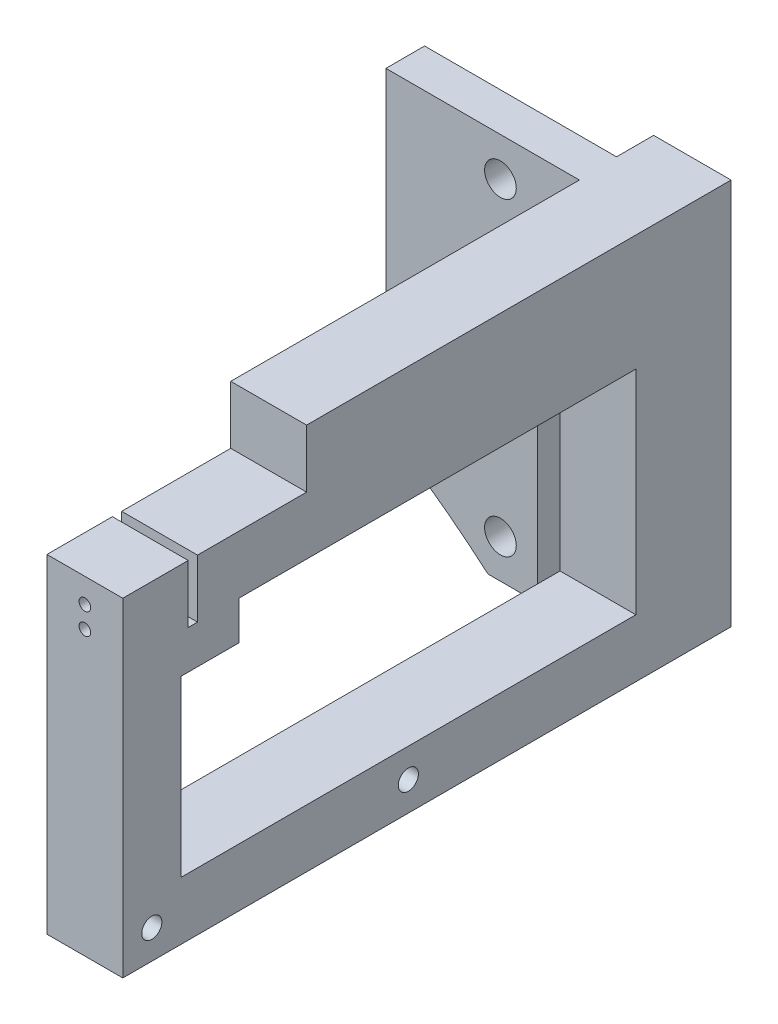
SolidWorks part; units mm, degrees
ref_plane "Front Plane" through (0, 0, 0) normal (0, 0, 1) x (1, 0, 0)
ref_plane "Top Plane" through (0, 0, 0) normal (0, 1, 0) x (1, 0, 0)
ref_plane "Right Plane" through (0, 0, 0) normal (1, 0, 0) x (0, 0, -1)
sketch "Sketch1" plane through (0, 0, 0) normal (0, 0, 1) x (1, 0, 0)
  line L0 (95.25, -31.75) -> (86.8503, -31.75) construction
  line L1 (94.996, -31.75) -> (86.8503, -31.75)
  line L2 (70.104, -19.2524) -> (70.104, -19.41)
  line L32 (70.104, 22.225) -> (70.104, 31.75)
  line L33 (70.104, -19.2524) -> (70.104, 22.225)
  line L34 (70.104, -19.2524) -> (70.104, 22.225)
  line L35 (101.6, 31.75) -> (3.175, 31.75) construction
  line L36 (101.6, 22.479) -> (101.6, 31.75)
  line L54 (70.104, 31.75) -> (101.6, 31.75)
  line L58 (94.996, 22.479) -> (101.6, 22.479)
  line L59 (94.996, -31.75) -> (94.996, 22.479)
  line L60 (94.996, 22.479) -> (101.6, 22.479)
  line L61 (94.996, -31.75) -> (94.996, 22.479)
  circle A0 centre (88.9, -25.4) radius 2.6 construction
  circle A1 centre (88.9, -25.4) radius 2.6
  circle A6 centre (88.9, 25.4) radius 2.6 construction
  circle A7 centre (88.9, 25.4) radius 2.6
  arc A8 (86.8503, -31.75) -> (69.85, -19.2524) centre (0, -132.08) ccw construction
  arc A9 (86.8503, -31.75) -> (70.104, -19.41) centre (0, -132.08) ccw
  dimension "D2" = 0.254
  dimension "D3" = 0.254
extrude "Boss-Extrude1" add sketch "Sketch1" along normal blind 6.35
sketch "Sketch2" plane through (0, 0, 6.35) normal (0, 0, 1) x (1, 0, 0)
  line L0 (101.6, 22.479) -> (101.854, 22.479)
  line L1 (94.996, 22.479) -> (101.6, 22.479) construction
  line L2 (101.854, 22.479) -> (101.854, -31.75)
  line L3 (101.854, -31.75) -> (114.3, -31.75)
  line L4 (114.3, -31.75) -> (114.3, 31.75)
  line L5 (114.3, 31.75) -> (101.6, 31.75)
  line L6 (101.6, 22.479) -> (101.6, 31.75) construction
  line L7 (101.6, 31.75) -> (101.6, 22.479)
  dimension "D1" = 12.7
  dimension "D2" = 0.254
extrude "Boss-Extrude2" add sketch "Sketch2" against normal offset from surface (12.446 mm away) 0.254
sketch "Sketch3" plane through (114.3, 0, 0) normal (1, 0, 0) x (0, 0, -1)
  line L0 (-6.35, -31.75) -> (-6.35, 22.225)
  line L1 (-93.725, -31.75) -> (-93.725, 22.225)
  line L2 (-93.725, 22.225) -> (-87.375, 22.225)
  line L4 (6.35, -31.75) -> (-93.725, -31.75) construction
  line L5 (-87.375, 22.225) -> (0, 22.225) construction
  line L6 (-84.2, 12.7) -> (-84.2, -22.225) construction
  line L7 (-84.2, -22.225) -> (-9.525, -22.225) construction
  line L8 (-9.525, 12.7) -> (-84.2, 12.7) construction
  line L9 (-9.525, -22.225) -> (-9.525, 12.7) construction
  line L10 (-6.35, -31.75) -> (-93.725, -31.75)
  line L11 (-87.375, 22.225) -> (-6.35, 22.225)
  line L12 (-84.2, 12.7) -> (-84.2, -22.225)
  line L13 (-84.2, -22.225) -> (-9.525, -22.225)
  line L14 (-9.525, 12.7) -> (-84.2, 12.7)
  line L15 (-9.525, -22.225) -> (-9.525, 12.7)
  line L16 (-87.375, 22.225) -> (0, 22.225) construction
  line L17 (-6.35, -31.75) -> (-6.35, 31.75) construction
  line L18 (-84.2, -4.7625) -> (-9.525, -4.7625)
extrude "Boss-Extrude4" add sketch "Sketch3" against normal offset from surface (12.446 mm away) 0.254 contours L11 L2 L1 L10 L8 L15 L13 L12 L14 region at (114.3, -30.723, 50.0375)
sketch "Sketch6" plane through (0, 22.225, 0) normal (0, 1, 0) x (1, 0, 0)
  line L1 (101.854, -6.35) -> (114.3, -6.35)
  line L2 (101.854, -6.35) -> (101.854, -63.5625)
  line L3 (101.854, -63.5625) -> (114.3, -63.5625)
  line L4 (114.3, -6.35) -> (114.3, -63.5625)
  line L5 (114.3, -93.725) -> (114.3, -6.35) construction
  line L6 (57.15, -65.15) -> (-95.25, -65.15) construction
  dimension "D1" = 1.5875
extrude "Boss-Extrude5" add sketch "Sketch6" along normal up to surface (9.525 mm away) up to face at (95.3347, 31.75, 0.0847)
sketch "Sketch7" plane through (114.3, 0, 0) normal (1, 0, 0) x (0, 0, -1)
  line L1 (-84.2, -22.225) -> (-9.525, -22.225) construction
  line L2 (-93.725, -31.75) -> (-93.725, 22.225) construction
  line L3 (-155.075, -31.75) -> (-45.075, -31.75) construction
  circle A0 centre (-88.9625, -26.9875) radius 1.65
  circle A1 centre (-46.8625, -26.9875) radius 1.65
  point P10 (-46.8625, -22.225)
  dimension "D3" = 3.3
  dimension "D1" = 4.7625
  dimension "D2" = 4.7625
extrude "Cut-Extrude2" cut sketch "Sketch7" against normal through all both
sketch "Sketch8" plane through (114.3, 0, 0) normal (1, 0, 0) x (0, 0, -1)
  line L0 (6.096, -31.75) -> (6.096, 31.75) construction
  line L1 (6.096, 31.75) -> (-63.5625, 31.75) construction
  line L2 (-63.5625, 31.75) -> (-63.5625, 22.225) construction
  line L3 (-93.725, 22.225) -> (-63.5625, 22.225) construction
  line L4 (6.096, 12.7) -> (6.096, 31.75)
  line L5 (6.096, 31.75) -> (-63.5625, 31.75)
  line L6 (-63.5625, 31.75) -> (-63.5625, 22.225)
  line L7 (-93.725, 22.225) -> (-63.5625, 22.225)
  line L8 (-9.525, 12.7) -> (-84.2, 12.7) construction
  line L9 (-93.725, -31.75) -> (-93.725, 22.225) construction
  line L10 (-9.525, 12.7) -> (-84.2, 12.7)
  line L11 (-93.725, 12.7) -> (-93.725, 22.225)
  line L12 (-84.2, 12.7) -> (-93.725, 12.7)
  line L13 (-9.525, 12.7) -> (6.096, 12.7)
  line L15 (-93.725, 12.7) -> (-74.675, 12.7)
  line L16 (-93.725, 12.7) -> (-93.725, 6.35)
  line L17 (-93.725, 6.35) -> (-74.675, 6.35)
  line L18 (-74.675, 12.7) -> (-74.675, 6.35)
  line M3 (6.096, 31.75) -> (-63.5625, 31.75)
  line M4 (-63.5625, 31.75) -> (-63.5625, 22.225)
  line M5 (-63.5625, 22.225) -> (-93.725, 22.225)
  line M6 (-93.725, 22.225) -> (-93.725, -31.75)
  line M8 (6.096, -31.75) -> (6.096, 31.75)
  line M11 (-84.2, -22.225) -> (-84.2, 12.7)
  line M12 (-84.2, 12.7) -> (-9.525, 12.7)
  dimension "D1" = 19.05
  dimension "D2" = 6.35
extrude "Boss-Extrude6" add sketch "Sketch8" against normal up to surface (12.446 mm away) contours L10 L13 L12 M12 M8 M3 M4 M5 M6 | L17 L12 M6 M11 | L18 L17 M12 M11 | L16 L15 L18 L17 region at (114.3, 21.3774, 37.6159) region at (114.3, 9.525, 79.4375) region at (114.3, 9.525, 88.9625) up to face at (101.854, -26.9875, 90.6125)
sketch "Sketch9" plane through (101.854, 0, 0) normal (-1, 0, 0) x (0, 0, 1)
  line L0 (82.225, 22.225) -> (82.225, 12.7)
  line L4 (93.725, -31.75) -> (93.725, 22.225) construction
  line L5 (93.725, 22.225) -> (63.5625, 22.225) construction
  dimension "D1" = 9.525
  dimension "D2" = 11.5
extrude "Cut-Extrude-Thin1" cut sketch "Sketch9" against normal through all both and the other way through all thin thin type mid plane wall 1.524
sketch "Sketch10" plane through (0, 0, 93.725) normal (0, 0, 1) x (1, 0, 0)
  line L0 (101.854, 22.225) -> (114.3, 22.225) construction
  line L1 (114.3, 12.7) -> (101.854, 12.7) construction
  line L2 (114.3, 22.225) -> (101.854, 22.225) construction
  circle A1 centre (108.077, 14.7) radius 0.95
  circle A2 centre (108.077, 18.225) radius 0.95
  point P7 (108.077, 22.225)
  dimension "D1" = 1.9
  dimension "D2" = 2
  dimension "D3" = 4
extrude "Cut-Extrude3" cut sketch "Sketch10" against normal up to surface (12.262 mm away) up to face at (108.077, 17.4625, 81.463)
equation "\"D3@Sketch7\"=3.3mm"
equation "\"D1@Sketch10\"=1.9mm"
equation "\"D3@Sketch10\"=4mm"
equation "\"D2@Sketch10\"=2mm"
